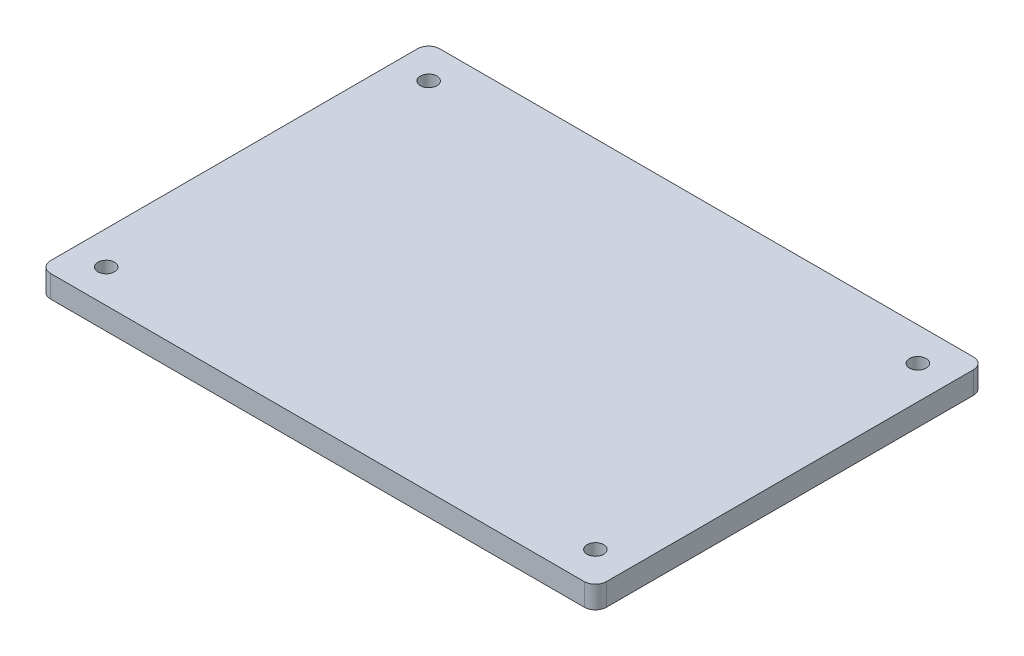
SolidWorks part; units mm, degrees
ref_plane "Alzado" through (0, 0, 0) normal (0, 0, 1) x (1, 0, 0)
ref_plane "Planta" through (0, 0, 0) normal (0, 1, 0) x (1, 0, 0)
ref_plane "Vista lateral" through (0, 0, 0) normal (1, 0, 0) x (0, 0, -1)
sketch "Croquis1" plane through (0, 0, 0) normal (0, 1, 0) x (1, 0, 0)
  line L1 (100, -70) -> (-100, -70)
  line L2 (100, -70) -> (100, 70)
  line L3 (100, 70) -> (-100, 70)
  line L4 (-100, -70) -> (-100, 70)
  line L5 (100, -70) -> (-100, 70) construction
  line L6 (100, 70) -> (-100, -70) construction
  point P0 (0, 0)
  dimension "D1" = 140
  dimension "D2" = 200
extrude "Saliente-Extruir1" add sketch "Croquis1" along normal blind 8
fillet "Redondeo1" radius 4 4 edges at (-100, 4, -70) (100, 4, -70) (100, 4, 70) (-100, 4, 70)
sketch "Croquis2" plane through (0, 8, 0) normal (0, 1, 0) x (1, 0, 0)
  line L0 (96, 70) -> (-96, 70) construction
  line L1 (100, -66) -> (100, 66) construction
  circle A0 centre (88, 58) radius 3
  point P4 (0, 0)
  point P6 (101.9419, 51.4757)
  dimension "D1" = 6
  dimension "D2" = 12
  dimension "D3" = 12
extrude "Cortar-Extruir1" cut sketch "Croquis2" against normal through all
mirror "Simetría1" about plane through (0, 0, 0) normal (0, 0, 1) of "Cortar-Extruir1"
mirror "Simetría2" about plane through (0, 0, 0) normal (1, 0, 0) of "Simetría1"
